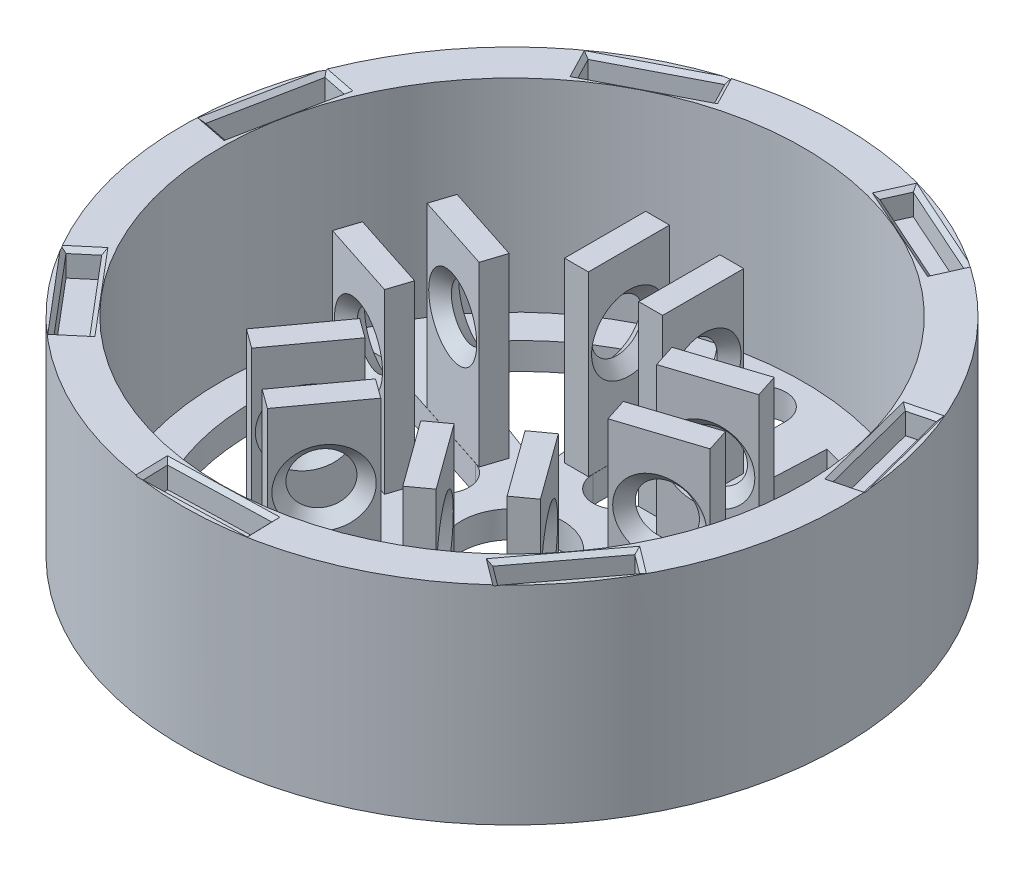
SolidWorks part; units mm, degrees
ref_plane "Front Plane" through (0, 0, 0) normal (0, 0, 1) x (1, 0, 0)
ref_plane "Top Plane" through (0, 0, 0) normal (0, 1, 0) x (1, 0, 0)
ref_plane "Right Plane" through (0, 0, 0) normal (1, 0, 0) x (0, 0, -1)
sketch "Sketch1" plane through (0, 0, 0) normal (0, 1, 0) x (1, 0, 0)
  circle A0 centre (0, 0) radius 65
  dimension "D1" = 130
extrude "Boss-Extrude1" add sketch "Sketch1" along normal blind 50
sketch "Sketch2" plane through (0, 0, 0) normal (0, -1, 0) x (1, 0, 0)
  circle A0 centre (0, 0) radius 57.5
  circle A1 centre (0, 0) radius 65
  dimension "D1" = 115
  dimension "D2" = 130
extrude "Cut-Extrude1" cut sketch "Sketch2" against normal blind 9
sketch "Sketch3" plane through (0, 50, 0) normal (0, 1, 0) x (1, 0, 0)
  circle A0 centre (0, 0) radius 57.5
  dimension "D1" = 115
extrude "Cut-Extrude2" cut sketch "Sketch3" against normal blind 40
sketch "Sketch5" plane through (0, 50, 0) normal (0, 1, 0) x (1, 0, 0)
  line L0 (-63.9038, 3.476) -> (-59, 2.5)
  line L1 (-59, 2.5) -> (-55.0962, 22.1153)
  line L2 (-55.0962, 22.1153) -> (-60, 23.0913)
  line L3 (-60, 23.0913) -> (-63.9038, 3.476)
  dimension "D1" = 5
  dimension "D2" = 5
  dimension "D3" = 20
  dimension "D4" = 20
  dimension "D5" = 2.5
  dimension "D6" = 59
  dimension "D7" = 60
extrude "Cut-Extrude4" cut sketch "Sketch5" against normal blind 5
sketch "Sketch7" plane through (0, 10, 0) normal (0, 1, 0) x (1, 0, 0)
  circle A0 centre (0, 0) radius 10
  dimension "D1" = 20
extrude "Cut-Extrude5" cut sketch "Sketch7" against normal through all
sketch "Sketch8" plane through (0, 10, 0) normal (0, 1, 0) x (1, 0, 0)
  line L5 (0, 49) -> (0, 21) construction
  line L6 (5, 49) -> (5, 21)
  line L7 (-5, 49) -> (-5, 21)
  arc A2 (5, 49) -> (-5, 49) centre (0, 49) ccw
  arc A3 (-5, 21) -> (5, 21) centre (0, 21) ccw
  point P2 (0, 35)
  point P7 (0, 16)
  dimension "D1" = 10
  dimension "D2" = 28
  dimension "D3" = 35
extrude "Cut-Extrude6" cut sketch "Sketch8" against normal through all
pattern_circular "CirPattern3" count 5 over 360 about axis through (0, 10, 0) along (0, 1, 0) of "Cut-Extrude6"
pattern_circular "CirPattern4" count 7 over 360 about axis through (0, 10, 0) along (0, 1, 0) of "Cut-Extrude4"
chamfer "Chamfer6" distance 0.8 angle 45 28 edges at (-35.9785, 50, -49.908) (-25.9464, 50, -52.2757) (-18.2087, 50, -59.0858) (-28.2408, 50, -56.7182) (16.5874, 50, -59.2463) (24.6935, 50, -52.8791) (34.8422, 50, -51.0755) (26.7362, 50, -57.4428) (56.6627, 50, -23.9709) (56.7386, 50, -13.6634) (61.6562, 50, -4.6043) (61.5803, 50, -14.9118) (54.0698, 50, 29.3551) (46.0585, 50, 35.841) (42.0418, 50, 45.334) (50.0532, 50, 38.848) (10.7613, 50, 60.5761) (0.6953, 50, 58.3565) (-9.2309, 50, 61.1349) (0.835, 50, 63.3545) (-40.6507, 50, 46.1821) (-45.1914, 50, 36.9283) (-53.5526, 50, 30.9) (-49.0119, 50, 40.1538) (-61.4519, 50, -2.988) (-57.0481, 50, -12.3077) (-57.5481, 50, -22.6033) (-61.9519, 50, -13.2836)
scale "Scale1" scale about centroid uniform scaling yes scale factor 0.75
sketch "Sketch9" plane through (0, 12.2247, 0) normal (0, 1, 0) x (1, 0, 0)
  line L0 (-38.1511, 1.1051) -> (-17.1482, -3.4914)
  line L1 (-29.6754, -23.2361) -> (-16.2803, -6.4188)
  arc A0 (-16.2803, -6.4188) -> (-17.1482, -3.4914) centre (-10.7679, -3.1922) cw
  arc A1 (-29.6754, -23.2361) -> (-38.1511, 1.1051) centre (-2.8887, -0.2627) cw
  dimension "D4" = 17.5
  dimension "D5" = 17.5
  dimension "D6" = 6.3873
  dimension "D7" = 35.2889
  dimension "D2" = 21.5
  dimension "D3" = 21.5
extrude "Cut-Extrude7" cut sketch "Sketch9" against normal through all
pattern_circular "CirPattern5" count 5 over 360 about axis through (0, 12.2247, 0) along (0, 1, 0) of "Cut-Extrude7"
scale "Scale2" scale about centroid uniform scaling yes scale factor 0.85
sketch "Sketch14" plane through (0, 7.0995, 0) normal (0, -1, 0) x (-1, 0, 0)
  circle A0 centre (0, 0) radius 36.6563
extrude "Cut-Extrude8" cut sketch "Sketch14" against normal blind 3
sketch "Sketch18" plane through (0, 13.4745, 0) normal (0, 1, 0) x (1, 0, 0)
  line L1 (-6.2, 23) -> (-3.2, 23)
  line L2 (-6.2, 23) -> (-6.2, 12.8)
  line L3 (-6.2, 12.8) -> (-3.2, 12.8)
  line L4 (-3.2, 23) -> (-3.2, 12.8)
  line L5 (3.2, 12.7311) -> (6.2, 12.7311)
  line L6 (3.2, 12.7311) -> (3.2, 22.9311)
  line L7 (3.2, 22.9311) -> (6.2, 22.9311)
  line L8 (6.2, 12.7311) -> (6.2, 22.9311)
  point P4 (-4.7, 12.8)
  dimension "D1" = 10.2
  dimension "D2" = 10.2
  dimension "D3" = 3
  dimension "D4" = 3
  dimension "D5" = 6.4
  dimension "D6" = 3.2
  dimension "D7" = 12.8
extrude "Boss-Extrude2" add sketch "Sketch18" along normal blind 22.3
sketch "Sketch19" plane through (-6.2, 0, 0) normal (-1, 0, 0) x (0, 0, 1)
  line L1 (-23, 13.4745) -> (-12.8, 13.4745) construction
  circle A0 centre (-17.9, 26.5745) radius 3.2
  dimension "D3" = 6.4
  dimension "D1" = 13.1
  dimension "D2" = 5.1
extrude "Cut-Extrude9" cut sketch "Sketch19" against normal blind 22.3
chamfer "Chamfer7" distance 1.5 angle 45 1 edges at (-6.2, 26.5745, -14.7)
chamfer "Chamfer8" distance 1.5 angle 45 3 edges at (3.2, 26.5745, -21.1) (6.2, 26.5745, -14.7) (-3.2, 26.5745, -14.7)
pattern_circular "CirPattern6" count 5 over 360 about axis through (0, 7.0995, 0) along (0, 1, 0) of "Chamfer8", "Chamfer7", "Cut-Extrude9", "Boss-Extrude2" reverse direction yes
ref_plane "Plane1" through (3.2, 35.7745, -12.7311) normal (0, 0, 1) x (1, 0, 0)
